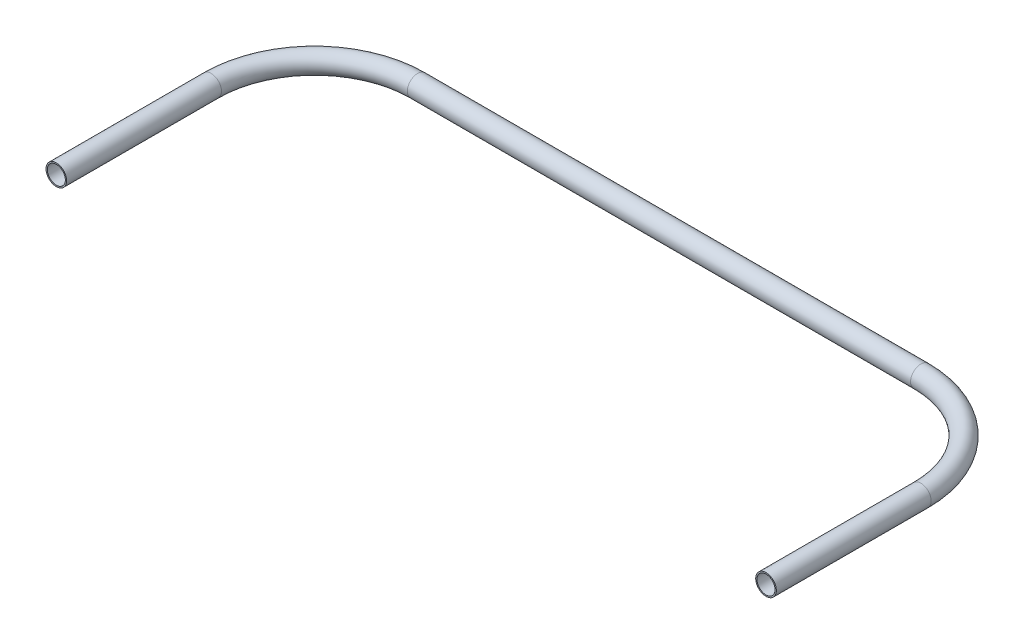
SolidWorks part; units mm, degrees
ref_plane "Спереди" through (0, 0, 0) normal (0, 0, 1) x (1, 0, 0)
ref_plane "Сверху" through (0, 0, 0) normal (0, 1, 0) x (1, 0, 0)
ref_plane "Справа" through (0, 0, 0) normal (1, 0, 0) x (0, 0, -1)
sketch "Эскиз1" plane through (0, 0, 0) normal (0, 1, 0) x (1, 0, 0)
  line L0 (-275, -200) -> (-275, -80)
  line L1 (0, 0) -> (-195, 0)
  line L2 (0, 0) -> (0, -87.0881) construction
  line L3 (275, -200) -> (275, -80) construction
  line L4 (195, 0) -> (0, 0) construction
  arc A0 (-275, -80) -> (-195, 0) centre (-195, -80) cw
  arc A1 (275, -80) -> (195, 0) centre (195, -80) ccw construction
  point P8 (0, 0)
  point P10 (0, 0)
  dimension "D1" = 80
  dimension "D2" = 550
  dimension "D3" = 200
sketch "Эскиз2" plane through (0, 0, 0) normal (1, 0, 0) x (0, 0, -1)
  circle A0 centre (0, 0) radius 8
  circle A1 centre (0, 0) radius 7
  dimension "D1" = 16
  dimension "D2" = 1
sweep "По траектории1" add profiles "Эскиз2" path "Эскиз1"
mirror "Зеркальное отражение1" about plane through (0, 0, 0) normal (1, 0, 0) of bodies 103
